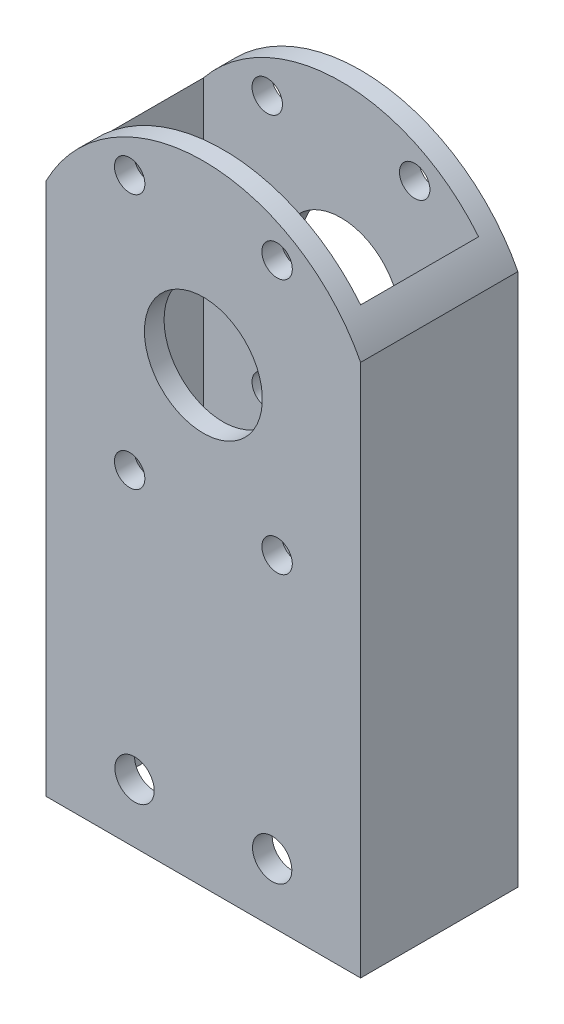
SolidWorks part; units mm, degrees
material "6061-T6 (SS)"
ref_plane "Front" through (0, 0, 0) normal (0, 0, 1) x (1, 0, 0)
ref_plane "Top" through (0, 0, 0) normal (0, 1, 0) x (1, 0, 0)
ref_plane "Right" through (0, 0, 0) normal (1, 0, 0) x (0, 0, -1)
sketch "Sketch1" plane through (0, 0, 0) normal (0, 1, 0) x (1, 0, 0)
  line L1 (-25.4, -12.7) -> (25.4, -12.7)
  line L2 (-25.4, -12.7) -> (-25.4, 12.7)
  line L3 (-25.4, 12.7) -> (25.4, 12.7)
  line L4 (25.4, -12.7) -> (25.4, 12.7)
  line L5 (-25.4, -12.7) -> (25.4, 12.7) construction
  line L6 (-25.4, 12.7) -> (25.4, -12.7) construction
  point P0 (0, 0)
  dimension "D1" = 25.4
  dimension "D2" = 50.8
extrude "Extrude-Thin1" add sketch "Sketch1" along normal blind 101.6 thin thin type one direction reverse wall 3.175
sketch "Sketch2" plane through (0, 0, -12.7) normal (0, 0, -1) x (-1, 0, 0)
  line L0 (0, 101.6) -> (0, 69.85)
  line L1 (-25.4, 101.6) -> (25.4, 101.6) construction
  line L3 (0, 60.325) -> (0, 79.375) construction
  circle A1 centre (0, 69.85) radius 23.8125
  circle A3 centre (0, 69.85) radius 9.525
  point P12 (0, 69.85)
  dimension "D1" = 19.05
  dimension "D3" = 47.625
  dimension "D2" = 31.75
hole_wizard "#10 (0.1935) Diameter Hole2" positions "Sketch5" profile "Sketch6" hole size "#10" standard "ANSI Inch" end condition through all
sketch "Sketch5" plane through (0, 0, -12.7) normal (0, 0, -1) x (-1, 0, 0)
  line L0 (0, 101.6) -> (0, 73.025)
  line L1 (-25.4, 101.6) -> (25.4, 101.6) construction
  line L3 (-11.9063, 93.6472) -> (11.9063, 93.6472)
  line L4 (-11.9063, 93.6472) -> (-11.9063, 52.4028)
  line L5 (-11.9063, 52.4028) -> (11.9063, 52.4028)
  line L6 (11.9063, 93.6472) -> (11.9063, 52.4028)
  circle A0 centre (0, 73.025) radius 23.8125
  point P21 (-11.9063, 93.6472)
  point P22 (11.9063, 93.6472)
  point P24 (11.9063, 52.4028)
  point P25 (-11.9063, 52.4028)
  point P47 (0, 0)
  point P48 (0, 0)
  point P49 (11.8972, 52.3975)
  point P50 (-12.0007, 52.4576)
  point P51 (-11.9063, 93.6472)
  dimension "D1" = 47.625
  dimension "D2" = 28.575
  dimension "D3" = 23.8125
sketch "Sketch6" plane through (11.9063, 52.4028, -12.7) normal (1, 0, 0) x (0, 1, 0)
  line L0 (0, 0) -> (0, 25.4)
  line L1 (0, 25.4) -> (2.4574, 25.4)
  line L2 (2.4574, 25.4) -> (2.4574, 0)
  line L5 (2.4574, 0) -> (0, 0)
  line L11 (0, -6.35) -> (0, 107.95) construction
  dimension "Thru Hole Dia." = 4.9149
  dimension "Thru Hole Depth" = 25.4
sketch "Sketch7" plane through (0, 0, -12.7) normal (0, 0, -1) x (-1, 0, 0)
  line L0 (-11.9063, 93.6472) -> (11.9063, 52.4028) construction
  circle A1 centre (0, 73.025) radius 9.525
  point P9 (0, 73.025)
  dimension "D1" = 19.05
extrude "Cut-Extrude2" cut sketch "Sketch7" against normal through all both
hole_wizard "1/4 (0.25) Diameter Hole1" positions "Sketch8" profile "Sketch9" hole size "1/4" standard "ANSI Inch" end condition through all
sketch "Sketch8" plane through (0, 0, 12.7) normal (0, 0, 1) x (1, 0, 0)
  line L2 (-25.4, 101.6) -> (-25.4, 0) construction
  line L4 (-25.4, 0) -> (25.4, 0) construction
  point P0 (-11.1125, 9.525)
  point P2 (11.1125, 9.525)
  point P14 (-109.1715, 68.7854)
  dimension "D1" = 22.225
  dimension "D2" = 14.2875
  dimension "D3" = 9.525
sketch "Sketch9" plane through (-11.1125, 9.525, 12.7) normal (1, 0, 0) x (0, -1, 0)
  line L0 (0, 0) -> (0, 25.4)
  line L1 (0, 25.4) -> (3.175, 25.4)
  line L2 (3.175, 25.4) -> (3.175, 0)
  line L5 (3.175, 0) -> (0, 0)
  line L11 (0, -6.35) -> (0, 107.95) construction
  dimension "Thru Hole Dia." = 6.35
  dimension "Thru Hole Depth" = 25.4
sketch "Sketch10" plane through (0, 0, -12.7) normal (0, 0, -1) x (-1, 0, 0)
  line L0 (-25.4, 86.1159) -> (-25.4, 101.6)
  line L1 (-25.4, 101.6) -> (25.4, 101.6)
  line L2 (25.4, 101.6) -> (25.4, 86.1159)
  line L3 (25.4, 101.6) -> (25.4, 0) construction
  arc A0 (25.4, 86.1159) -> (-25.4, 86.1159) centre (0, 73.025) ccw
  line M13 (25.4, 0) -> (25.4, 101.6)
  line M14 (25.4, 101.6) -> (-25.4, 101.6)
  line M15 (-25.4, 101.6) -> (-25.4, 0)
extrude "Cut-Extrude3" cut sketch "Sketch10" against normal through all contours A0 L1 M15 | A0 M13 M14 region at (-19.4433, 97.2944, -12.7) region at (19.4433, 97.2944, -12.7)
